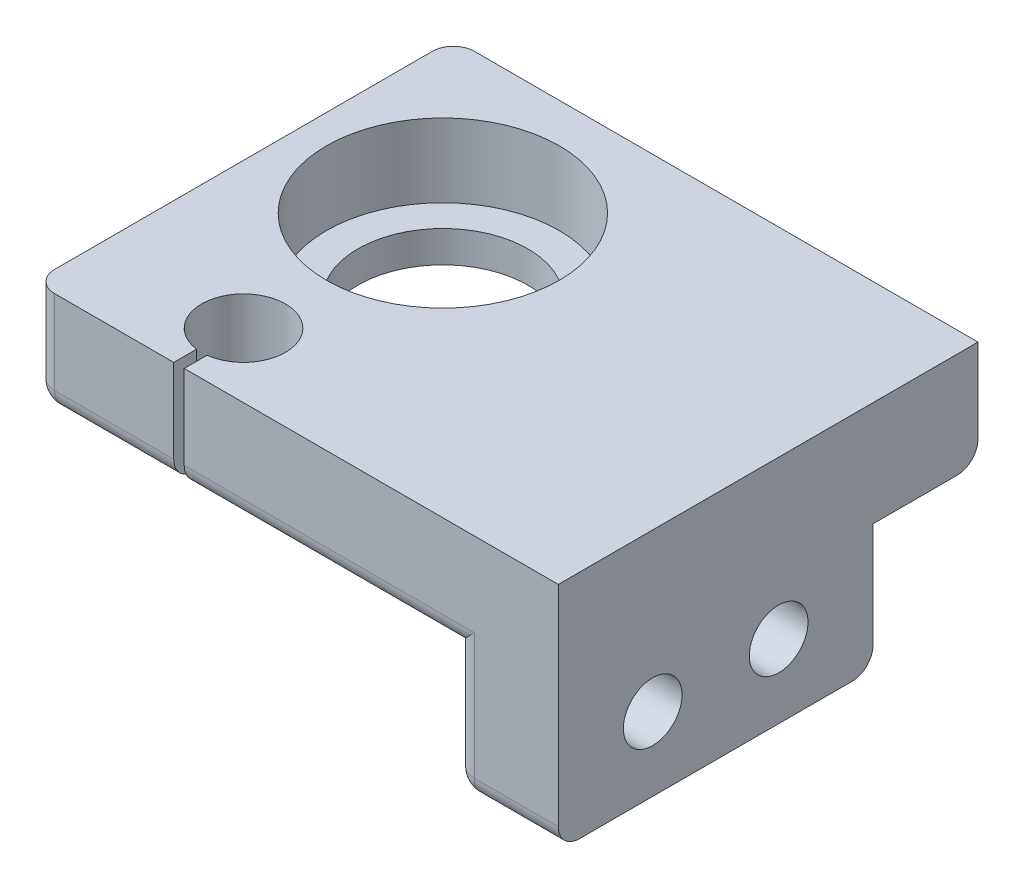
SolidWorks part; units mm, degrees
ref_plane "Front Plane" through (0, 0, 0) normal (0, 0, 1) x (1, 0, 0)
ref_plane "Top Plane" through (0, 0, 0) normal (0, 1, 0) x (1, 0, 0)
ref_plane "Right Plane" through (0, 0, 0) normal (1, 0, 0) x (0, 0, -1)
sketch "Sketch1" plane through (0, 0, 0) normal (0, 1, 0) x (1, 0, 0)
  line L0 (13.85, -14.85) -> (13.85, -33.85) construction
  line L1 (0, 0) -> (50, 0)
  line L2 (0, 0) -> (0, -40)
  line L3 (0, -40) -> (50, -40)
  line L4 (50, 0) -> (50, -40)
  line L5 (13.85, -33.85) -> (13.85, -40) construction
  line L6 (13.85, -14.85) -> (13.85, 0) construction
  line L8 (13.35, -37.8186) -> (14.35, -37.8186)
  line L9 (13.35, -37.8186) -> (13.35, -40)
  line L10 (13.35, -40) -> (14.35, -40)
  line L11 (14.35, -37.8186) -> (14.35, -40)
  circle A0 centre (13.85, -33.85) radius 4
  circle A1 centre (13.85, -14.85) radius 8.1
  circle A2 centre (13.85, -14.85) radius 11.1 construction
  dimension "D3" = 8
  dimension "D4" = 6.15
  dimension "D6" = 22.2
  dimension "D7" = 3
  dimension "D1" = 40
  dimension "D2" = 50
  dimension "D5" = 19
  dimension "D8" = 1
  dimension "D9" = 13.85
extrude "Boss-Extrude1" add sketch "Sketch1" along normal blind 10 contours A0 L1 L2 L3 L4 A1 region at (26.6554, 0, 20.1863)
sketch "Sketch2" plane through (0, 10, 0) normal (0, 1, 0) x (1, 0, 0)
  circle A0 centre (13.85, -14.85) radius 11.1 construction
  circle A1 centre (13.85, -14.85) radius 11.1
extrude "Cut-Extrude1" cut sketch "Sketch2" against normal blind 7
sketch "Sketch6" plane through (0, 0, 40) normal (0, 0, 1) x (1, 0, 0)
  line L1 (50, 0) -> (40, 0)
  line L2 (50, 0) -> (50, -12)
  line L3 (50, -12) -> (40, -12)
  line L4 (40, 0) -> (40, -12)
  dimension "D1" = 12
  dimension "D2" = 10
extrude "Boss-Extrude3" add sketch "Sketch6" against normal blind 30
sketch "Sketch7" plane through (40, 0, 0) normal (-1, 0, 0) x (0, 0, 1)
  line L0 (31, -5) -> (19, -5) construction
  line L1 (19, -5) -> (10, -5) construction
  line L2 (10, 0) -> (10, -12) construction
  line L3 (31, -5) -> (40, -5) construction
  line L4 (40, 0) -> (40, -12) construction
  line L5 (10, 0) -> (40, 0) construction
  circle A0 centre (19, -5) radius 2.8
  circle A1 centre (31, -5) radius 2.8
  dimension "D1" = 12
  dimension "D3" = 5.6
  dimension "D2" = 5
extrude "Cut-Extrude2" cut sketch "Sketch7" against normal through all
sketch "Sketch8" plane through (40, 0, 0) normal (-1, 0, 0) x (0, 0, 1)
  circle A0 centre (19, -5) radius 4.3
  circle A1 centre (31, -5) radius 4.3
  dimension "D1" = 8.6
extrude "Cut-Extrude3" cut sketch "Sketch8" against normal blind 6
fillet "Fillet1" radius 2 11 edges at (45, -12, 10) (45, -12, 40) (6.675, 0, 40) (27.175, 0, 40) (40, -6, 40) (40, -12, 25) (40, -6, 10) (0, 5, 40) (0, 5, 0) (25, 0, 0) (0, 0, 20)
